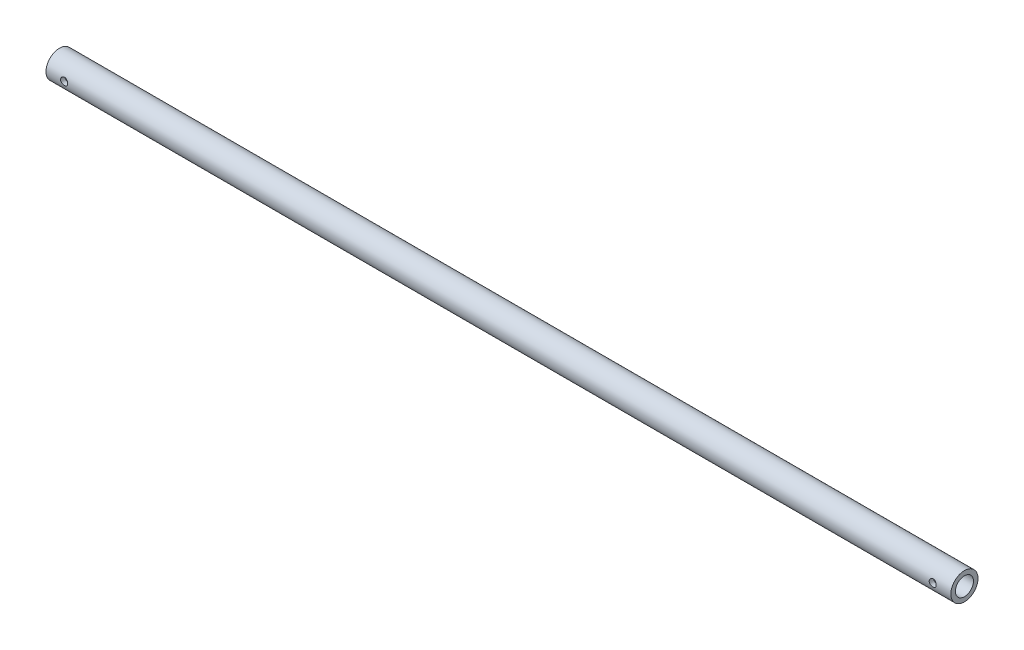
SolidWorks part; units mm, degrees
ref_plane "Front" through (0, 0, 0) normal (0, 0, 1) x (1, 0, 0)
ref_plane "Top" through (0, 0, 0) normal (0, 1, 0) x (1, 0, 0)
ref_plane "Right" through (0, 0, 0) normal (1, 0, 0) x (0, 0, -1)
sketch "Sketch1" plane through (0, 0, 0) normal (1, 0, 0) x (0, 0, -1)
  line L0 (6.35, 0) -> (9.525, 0) construction
  line L1 (6.35, 0) -> (9.525, 0) construction
  line L2 (7.9375, 0) -> (7.9375, 1.0672) construction
  circle A0 centre (0, 0) radius 9.525
  circle A1 centre (0, 0) radius 6.35
  point P4 (9.525, 0)
  point P5 (6.35, 0)
  dimension "OD" = 19.05
  dimension "ID" = 12.7
  dimension "Wall Thickness" = 3.175
sketch "Sketch2" plane through (0, 0, 0) normal (0, 0, 1) x (1, 0, 0)
  line L0 (-317.5, 0) -> (317.5, 0) construction
  point P2 (-293.6875, 0)
  point P3 (293.6875, 0)
  dimension "D1" = 23.8125
  dimension "D2" = 23.8125
sketch "Sketch3" plane through (0, 0, 0) normal (1, 0, 0) x (0, 0, -1)
  circle A0 centre (0, 0) radius 6.35 construction
  circle A1 centre (0, 0) radius 9.525 construction
  circle A2 centre (0, 0) radius 6.35
  circle A3 centre (0, 0) radius 9.525
extrude "Boss-Extrude1" add sketch "Sketch3" along normal mid plane 635
sketch "Sketch6" plane through (0, 0.3324, 12.6956) normal (0, 0.0262, 0.9997) x (1, 0, 0)
  circle A0 centre (-304.8, 0) radius 2.4892
extrude "Cut-Extrude1" cut sketch "Sketch6" against normal through all
sketch "Sketch7" plane through (0, 0.3324, 12.6956) normal (0, 0.0262, 0.9997) x (1, 0, 0)
  circle A0 centre (304.7404, 0) radius 2.4892
extrude "Cut-Extrude2" cut sketch "Sketch7" against normal through all
equation "\"D1@Boss-Extrude1\"=\"Length@Sketch2\""
equation "\"D1@Sketch2\"=\"OD@Sketch1\"*1.25"
equation "\"D2@Sketch2\"=\"D1@Sketch2\""
